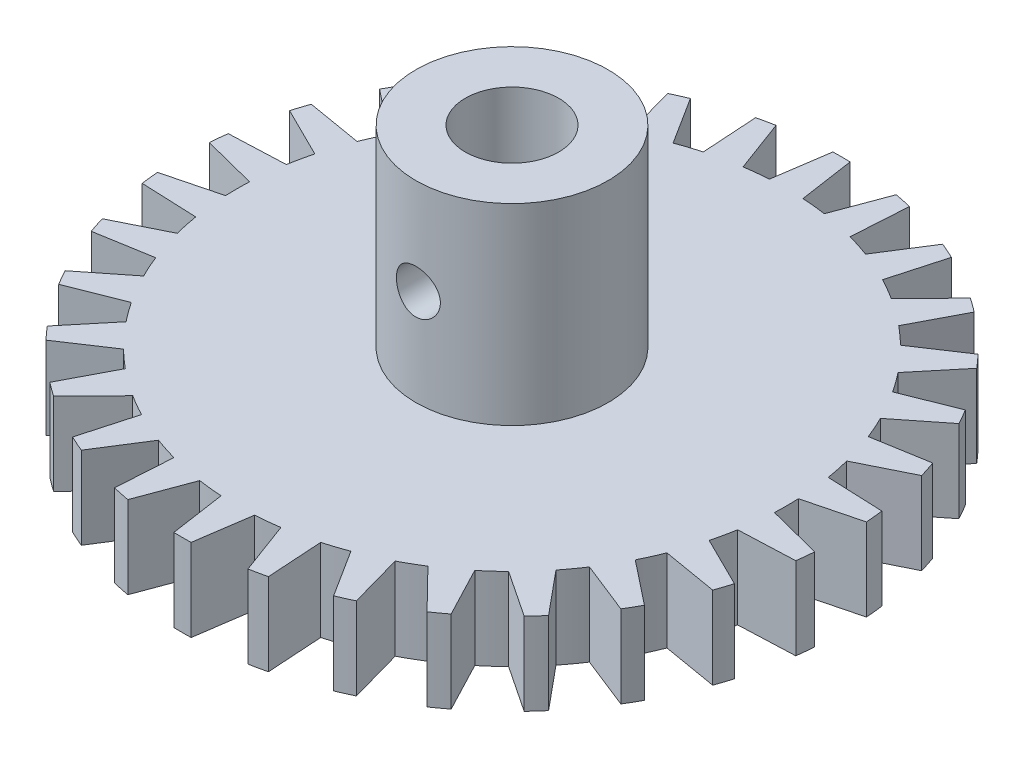
SolidWorks part; units mm, degrees
ref_plane "Front Plane" through (0, 0, 0) normal (0, 0, 1) x (1, 0, 0)
ref_plane "Top Plane" through (0, 0, 0) normal (0, 1, 0) x (1, 0, 0)
ref_plane "Right Plane" through (0, 0, 0) normal (1, 0, 0) x (0, 0, -1)
sketch "Sketch1" plane through (0, 0, 0) normal (0, 1, 0) x (1, 0, 0)
  line L0 (0, 0) -> (0, 12) construction
  line L1 (0, 0) -> (-0.3141, 11.9959) construction
  line L2 (0, 0) -> (-0.6105, 9.9813) construction
  line L3 (0, 0) -> (-1.0453, 9.9452) construction
  line L4 (-0.3141, 11.9959) -> (-0.6105, 9.9813)
  line L5 (0.3141, 11.9959) -> (0.6105, 9.9813)
  line L6 (2.1868, 11.7991) -> (1.4781, 9.8902)
  line L7 (2.8013, 11.6684) -> (2.6724, 9.6363)
  line L8 (4.5922, 11.0866) -> (3.5021, 9.3667)
  line L9 (5.1661, 10.831) -> (4.6175, 8.8701)
  line L10 (6.7969, 9.8895) -> (5.373, 8.4339)
  line L11 (7.3051, 9.5202) -> (6.3608, 7.7162)
  line L12 (8.7045, 8.2603) -> (7.0091, 7.1325)
  line L13 (9.1249, 7.7934) -> (7.8261, 6.2251)
  line L14 (10.2317, 6.27) -> (8.3389, 5.5194)
  line L15 (10.5458, 5.7259) -> (8.9493, 4.462)
  line L16 (11.3117, 4.0057) -> (9.3042, 3.665)
  line L17 (11.5058, 3.4082) -> (9.6815, 2.5038)
  line L18 (11.8973, 1.5663) -> (9.8629, 1.6505)
  line L19 (11.963, 0.9415) -> (9.9905, 0.4362)
  line L20 (11.963, -0.9415) -> (9.9905, -0.4362)
  line L21 (11.8973, -1.5663) -> (9.8629, -1.6505)
  line L22 (11.5058, -3.4082) -> (9.6815, -2.5038)
  line L23 (11.3117, -4.0057) -> (9.3042, -3.665)
  line L24 (10.5458, -5.7259) -> (8.9493, -4.462)
  line L25 (10.2317, -6.27) -> (8.3389, -5.5194)
  line L26 (9.1249, -7.7934) -> (7.8261, -6.2251)
  line L27 (8.7045, -8.2603) -> (7.0091, -7.1325)
  line L28 (7.3051, -9.5202) -> (6.3608, -7.7162)
  line L29 (6.7969, -9.8895) -> (5.373, -8.4339)
  line L30 (5.1661, -10.831) -> (4.6175, -8.8701)
  line L31 (4.5922, -11.0866) -> (3.5021, -9.3667)
  line L32 (2.8013, -11.6684) -> (2.6724, -9.6363)
  line L33 (2.1868, -11.7991) -> (1.4781, -9.8902)
  line L34 (0.3141, -11.9959) -> (0.6105, -9.9813)
  line L35 (-0.3141, -11.9959) -> (-0.6105, -9.9813)
  line L36 (-2.1868, -11.7991) -> (-1.4781, -9.8902)
  line L37 (-2.8013, -11.6684) -> (-2.6724, -9.6363)
  line L38 (-4.5922, -11.0866) -> (-3.5021, -9.3667)
  line L39 (-5.1661, -10.831) -> (-4.6175, -8.8701)
  line L40 (-6.7969, -9.8895) -> (-5.373, -8.4339)
  line L41 (-7.3051, -9.5202) -> (-6.3608, -7.7162)
  line L42 (-8.7045, -8.2603) -> (-7.0091, -7.1325)
  line L43 (-9.1249, -7.7934) -> (-7.8261, -6.2251)
  line L44 (-10.2317, -6.27) -> (-8.3389, -5.5194)
  line L45 (-10.5458, -5.7259) -> (-8.9493, -4.462)
  line L46 (-11.3117, -4.0057) -> (-9.3042, -3.665)
  line L47 (-11.5058, -3.4082) -> (-9.6815, -2.5038)
  line L48 (-11.8973, -1.5663) -> (-9.8629, -1.6505)
  line L49 (-11.963, -0.9415) -> (-9.9905, -0.4362)
  line L50 (-11.963, 0.9415) -> (-9.9905, 0.4362)
  line L51 (-11.8973, 1.5663) -> (-9.8629, 1.6505)
  line L52 (-11.5058, 3.4082) -> (-9.6815, 2.5038)
  line L53 (-11.3117, 4.0057) -> (-9.3042, 3.665)
  line L54 (-10.5458, 5.7259) -> (-8.9493, 4.462)
  line L55 (-10.2317, 6.27) -> (-8.3389, 5.5194)
  line L56 (-9.1249, 7.7934) -> (-7.8261, 6.2251)
  line L57 (-8.7045, 8.2603) -> (-7.0091, 7.1325)
  line L58 (-7.3051, 9.5202) -> (-6.3608, 7.7162)
  line L59 (-6.7969, 9.8895) -> (-5.373, 8.4339)
  line L60 (-5.1661, 10.831) -> (-4.6175, 8.8701)
  line L61 (-4.5922, 11.0866) -> (-3.5021, 9.3667)
  line L62 (-2.8013, 11.6684) -> (-2.6724, 9.6363)
  line L63 (-2.1868, 11.7991) -> (-1.4781, 9.8902)
  arc A0 (0.3141, 11.9959) -> (-0.3141, 11.9959) centre (0, 0) ccw
  arc A1 (-0.6105, 9.9813) -> (-1.0453, 9.9452) centre (0, 0) ccw
  arc A2 (0.6105, 9.9813) -> (1.0453, 9.9452) centre (0, 0) cw
  arc A4 (2.8013, 11.6684) -> (2.1868, 11.7991) centre (0, 0) ccw
  arc A5 (1.4781, 9.8902) -> (1.0453, 9.9452) centre (0, 0) ccw
  arc A6 (2.6724, 9.6363) -> (3.0902, 9.5106) centre (0, 0) cw
  arc A7 (5.1661, 10.831) -> (4.5922, 11.0866) centre (0, 0) ccw
  arc A8 (3.5021, 9.3667) -> (3.0902, 9.5106) centre (0, 0) ccw
  arc A9 (4.6175, 8.8701) -> (5, 8.6603) centre (0, 0) cw
  arc A10 (7.3051, 9.5202) -> (6.7969, 9.8895) centre (0, 0) ccw
  arc A11 (5.373, 8.4339) -> (5, 8.6603) centre (0, 0) ccw
  arc A12 (6.3608, 7.7162) -> (6.6913, 7.4314) centre (0, 0) cw
  arc A13 (9.1249, 7.7934) -> (8.7045, 8.2603) centre (0, 0) ccw
  arc A14 (7.0091, 7.1325) -> (6.6913, 7.4314) centre (0, 0) ccw
  arc A15 (7.8261, 6.2251) -> (8.0902, 5.8779) centre (0, 0) cw
  arc A16 (10.5458, 5.7259) -> (10.2317, 6.27) centre (0, 0) ccw
  arc A17 (8.3389, 5.5194) -> (8.0902, 5.8779) centre (0, 0) ccw
  arc A18 (8.9493, 4.462) -> (9.1355, 4.0674) centre (0, 0) cw
  arc A19 (11.5058, 3.4082) -> (11.3117, 4.0057) centre (0, 0) ccw
  arc A20 (9.3042, 3.665) -> (9.1355, 4.0674) centre (0, 0) ccw
  arc A21 (9.6815, 2.5038) -> (9.7815, 2.0791) centre (0, 0) cw
  arc A22 (11.963, 0.9415) -> (11.8973, 1.5663) centre (0, 0) ccw
  arc A23 (9.8629, 1.6505) -> (9.7815, 2.0791) centre (0, 0) ccw
  arc A24 (9.9905, 0.4362) -> (10, 0) centre (0, 0) cw
  arc A25 (11.8973, -1.5663) -> (11.963, -0.9415) centre (0, 0) ccw
  arc A26 (9.9905, -0.4362) -> (10, 0) centre (0, 0) ccw
  arc A27 (9.8629, -1.6505) -> (9.7815, -2.0791) centre (0, 0) cw
  arc A28 (11.3117, -4.0057) -> (11.5058, -3.4082) centre (0, 0) ccw
  arc A29 (9.6815, -2.5038) -> (9.7815, -2.0791) centre (0, 0) ccw
  arc A30 (9.3042, -3.665) -> (9.1355, -4.0674) centre (0, 0) cw
  arc A31 (10.2317, -6.27) -> (10.5458, -5.7259) centre (0, 0) ccw
  arc A32 (8.9493, -4.462) -> (9.1355, -4.0674) centre (0, 0) ccw
  arc A33 (8.3389, -5.5194) -> (8.0902, -5.8779) centre (0, 0) cw
  arc A34 (8.7045, -8.2603) -> (9.1249, -7.7934) centre (0, 0) ccw
  arc A35 (7.8261, -6.2251) -> (8.0902, -5.8779) centre (0, 0) ccw
  arc A36 (7.0091, -7.1325) -> (6.6913, -7.4314) centre (0, 0) cw
  arc A37 (6.7969, -9.8895) -> (7.3051, -9.5202) centre (0, 0) ccw
  arc A38 (6.3608, -7.7162) -> (6.6913, -7.4314) centre (0, 0) ccw
  arc A39 (5.373, -8.4339) -> (5, -8.6603) centre (0, 0) cw
  arc A40 (4.5922, -11.0866) -> (5.1661, -10.831) centre (0, 0) ccw
  arc A41 (4.6175, -8.8701) -> (5, -8.6603) centre (0, 0) ccw
  arc A42 (3.5021, -9.3667) -> (3.0902, -9.5106) centre (0, 0) cw
  arc A43 (2.1868, -11.7991) -> (2.8013, -11.6684) centre (0, 0) ccw
  arc A44 (2.6724, -9.6363) -> (3.0902, -9.5106) centre (0, 0) ccw
  arc A45 (1.4781, -9.8902) -> (1.0453, -9.9452) centre (0, 0) cw
  arc A46 (-0.3141, -11.9959) -> (0.3141, -11.9959) centre (0, 0) ccw
  arc A47 (0.6105, -9.9813) -> (1.0453, -9.9452) centre (0, 0) ccw
  arc A48 (-0.6105, -9.9813) -> (-1.0453, -9.9452) centre (0, 0) cw
  arc A49 (-2.8013, -11.6684) -> (-2.1868, -11.7991) centre (0, 0) ccw
  arc A50 (-1.4781, -9.8902) -> (-1.0453, -9.9452) centre (0, 0) ccw
  arc A51 (-2.6724, -9.6363) -> (-3.0902, -9.5106) centre (0, 0) cw
  arc A52 (-5.1661, -10.831) -> (-4.5922, -11.0866) centre (0, 0) ccw
  arc A53 (-3.5021, -9.3667) -> (-3.0902, -9.5106) centre (0, 0) ccw
  arc A54 (-4.6175, -8.8701) -> (-5, -8.6603) centre (0, 0) cw
  arc A55 (-7.3051, -9.5202) -> (-6.7969, -9.8895) centre (0, 0) ccw
  arc A56 (-5.373, -8.4339) -> (-5, -8.6603) centre (0, 0) ccw
  arc A57 (-6.3608, -7.7162) -> (-6.6913, -7.4314) centre (0, 0) cw
  arc A58 (-9.1249, -7.7934) -> (-8.7045, -8.2603) centre (0, 0) ccw
  arc A59 (-7.0091, -7.1325) -> (-6.6913, -7.4314) centre (0, 0) ccw
  arc A60 (-7.8261, -6.2251) -> (-8.0902, -5.8779) centre (0, 0) cw
  arc A61 (-10.5458, -5.7259) -> (-10.2317, -6.27) centre (0, 0) ccw
  arc A62 (-8.3389, -5.5194) -> (-8.0902, -5.8779) centre (0, 0) ccw
  arc A63 (-8.9493, -4.462) -> (-9.1355, -4.0674) centre (0, 0) cw
  arc A64 (-11.5058, -3.4082) -> (-11.3117, -4.0057) centre (0, 0) ccw
  arc A65 (-9.3042, -3.665) -> (-9.1355, -4.0674) centre (0, 0) ccw
  arc A66 (-9.6815, -2.5038) -> (-9.7815, -2.0791) centre (0, 0) cw
  arc A67 (-11.963, -0.9415) -> (-11.8973, -1.5663) centre (0, 0) ccw
  arc A68 (-9.8629, -1.6505) -> (-9.7815, -2.0791) centre (0, 0) ccw
  arc A69 (-9.9905, -0.4362) -> (-10, 0) centre (0, 0) cw
  arc A70 (-11.8973, 1.5663) -> (-11.963, 0.9415) centre (0, 0) ccw
  arc A71 (-9.9905, 0.4362) -> (-10, 0) centre (0, 0) ccw
  arc A72 (-9.8629, 1.6505) -> (-9.7815, 2.0791) centre (0, 0) cw
  arc A73 (-11.3117, 4.0057) -> (-11.5058, 3.4082) centre (0, 0) ccw
  arc A74 (-9.6815, 2.5038) -> (-9.7815, 2.0791) centre (0, 0) ccw
  arc A75 (-9.3042, 3.665) -> (-9.1355, 4.0674) centre (0, 0) cw
  arc A76 (-10.2317, 6.27) -> (-10.5458, 5.7259) centre (0, 0) ccw
  arc A77 (-8.9493, 4.462) -> (-9.1355, 4.0674) centre (0, 0) ccw
  arc A78 (-8.3389, 5.5194) -> (-8.0902, 5.8779) centre (0, 0) cw
  arc A79 (-8.7045, 8.2603) -> (-9.1249, 7.7934) centre (0, 0) ccw
  arc A80 (-7.8261, 6.2251) -> (-8.0902, 5.8779) centre (0, 0) ccw
  arc A81 (-7.0091, 7.1325) -> (-6.6913, 7.4314) centre (0, 0) cw
  arc A82 (-6.7969, 9.8895) -> (-7.3051, 9.5202) centre (0, 0) ccw
  arc A83 (-6.3608, 7.7162) -> (-6.6913, 7.4314) centre (0, 0) ccw
  arc A84 (-5.373, 8.4339) -> (-5, 8.6603) centre (0, 0) cw
  arc A85 (-4.5922, 11.0866) -> (-5.1661, 10.831) centre (0, 0) ccw
  arc A86 (-4.6175, 8.8701) -> (-5, 8.6603) centre (0, 0) ccw
  arc A87 (-3.5021, 9.3667) -> (-3.0902, 9.5106) centre (0, 0) cw
  arc A88 (-2.1868, 11.7991) -> (-2.8013, 11.6684) centre (0, 0) ccw
  arc A89 (-2.6724, 9.6363) -> (-3.0902, 9.5106) centre (0, 0) ccw
  arc A90 (-1.4781, 9.8902) -> (-1.0453, 9.9452) centre (0, 0) cw
  point P185 (0, 0)
  dimension "D1" = 1.5
  dimension "D2" = 2
  dimension "D3" = 2.5
  dimension "D4" = 30
  dimension "D5" = 10
extrude "Boss-Extrude1" add sketch "Sketch1" along normal blind 3
sketch "Sketch3" plane through (0, 3, 0) normal (0, 1, 0) x (1, 0, 0)
  circle A1 centre (0, 0) radius 3.5
  dimension "D2" = 7
extrude "Boss-Extrude2" add sketch "Sketch3" along normal blind 7
sketch "Sketch2" plane through (0, 3, 0) normal (0, 1, 0) x (1, 0, 0)
  circle A0 centre (0, 0) radius 1.7
  dimension "D1" = 3.4
extrude "Cut-Extrude1" cut sketch "Sketch2" against normal through all and the other way through all
sketch "Sketch4" plane through (0, 0, 0) normal (0, 0, 1) x (1, 0, 0)
  line L1 (3.5, 10) -> (-3.5, 10) construction
  circle A0 centre (0, 6.5) radius 0.8
  dimension "D1" = 1.6
  dimension "D2" = 3.5
extrude "Cut-Extrude2" cut sketch "Sketch4" along normal through all
